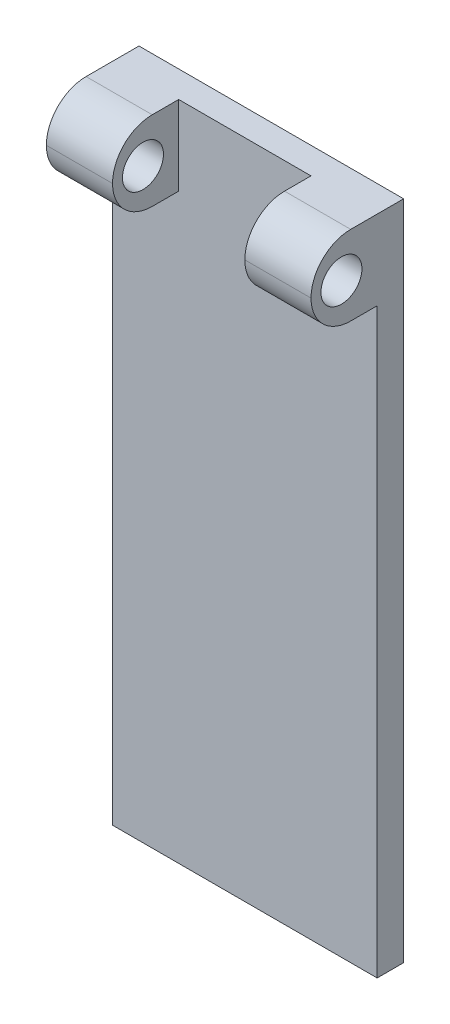
SolidWorks part; units mm, degrees
ref_plane "Front Plane" through (0, 0, 0) normal (0, 0, 1) x (1, 0, 0)
ref_plane "Top Plane" through (0, 0, 0) normal (0, 1, 0) x (1, 0, 0)
ref_plane "Right Plane" through (0, 0, 0) normal (1, 0, 0) x (0, 0, -1)
sketch "Sketch1" plane through (0, 0, 0) normal (0, 0, 1) x (1, 0, 0)
  line L0 (0, 0) -> (0, 25) construction
  line L1 (-10, -25) -> (10, -25)
  line L2 (-10, -25) -> (-10, 25)
  line L3 (-10, 25) -> (10, 25)
  line L4 (10, -25) -> (10, 25)
  line L5 (-10, -25) -> (10, 25) construction
  line L6 (-10, 25) -> (10, -25) construction
  line L7 (-5, 25) -> (5, 25)
  line L8 (-5, 25) -> (-5, 0)
  line L9 (-5, 0) -> (5, 0)
  line L10 (5, 25) -> (5, 0)
  point P0 (0, 0)
  point P12 (0, 0)
  point P13 (0, 0)
  point P14 (0, 0)
  dimension "D1" = 50
  dimension "D2" = 10
  dimension "D3" = 20
extrude "Boss-Extrude1" add sketch "Sketch1" along normal blind 5 contours L3 L10 L9 L8 L2 L1 L4 region at (0, -4.1667, 0)
extrude "Boss-Extrude2" add sketch "Sketch1<3>" against normal blind 2 contours L3 L10 L9 L8 L2 L1 L4 | L10 L3 L8 L9 region at (0, -4.1667, 0) region at (0, 12.5, 0)
sketch "Sketch1<3>" plane through (0, 0, 0) normal (0, 0, 1) x (1, 0, 0) same geometry as "Sketch1"
sketch "Sketch2" plane through (10, 0, 0) normal (1, 0, 0) x (0, 0, -1)
  line L0 (-5, 25) -> (0, 25) construction
  line L1 (-5, 25) -> (0, 25)
  line L2 (0, 25) -> (0, -15) construction
  circle A0 centre (-2.7, 22) radius 1.55
  point P3 (-1.8785, 12)
  point P8 (0, 0)
  dimension "D1" = 3.1
  dimension "D2" = 3
  dimension "D3" = 2.7
extrude "Cut-Extrude1" cut sketch "Sketch2" against normal through all contours A0 region at (10, 22, 2.7)
sketch "Sketch3" plane through (0, 0, 5) normal (0, 0, 1) x (1, 0, 0)
  line L0 (10, 19) -> (-10, 19)
  line L2 (-10, -25) -> (-10, 25) construction
  line L3 (10, -25) -> (10, 25) construction
  line L8 (10, 25) -> (5, 25)
  line L9 (5, 25) -> (5, 0)
  line L10 (5, 0) -> (-5, 0)
  line L11 (-5, 0) -> (-5, 25)
  line L12 (-5, 25) -> (-10, 25)
  line L13 (-10, 25) -> (-10, -25)
  line L14 (-10, -25) -> (10, -25)
  line L15 (10, -25) -> (10, 25)
  line L16 (10, 25) -> (5, 25) construction
  line L17 (5, 19) -> (5, 0)
  line L18 (5, 0) -> (-5, 0)
  line L19 (-5, 0) -> (-5, 19)
  line L20 (-5, 25) -> (-10, 25) construction
  line L21 (-10, 19) -> (-10, -25)
  line L22 (-10, -25) -> (10, -25)
  line L23 (10, -25) -> (10, 19)
  point P6 (10, 8.7855)
  point P10 (-10, 9.0405)
  line M11 (5, 25) -> (5, 0)
  line M12 (5, 0) -> (-5, 0)
  line M13 (-5, 0) -> (-5, 25)
  line M15 (-10, 25) -> (-10, -25)
  line M16 (-10, -25) -> (10, -25)
  line M17 (10, -25) -> (10, 25)
  dimension "D2" = 6
  dimension "D1" = 0
extrude "Cut-Extrude3" cut sketch "Sketch3" against normal up to surface (5 mm away) contours L0 M17 M11 M12 M13 M15 M16 region at (0, -6.442, 5) up to face at (0, 12.5, 0)
fillet "Fillet1" radius 3 4 edges at (-7.5, 19, 5) (-7.5, 25, 5) (7.5, 25, 5) (7.5, 19, 5)
